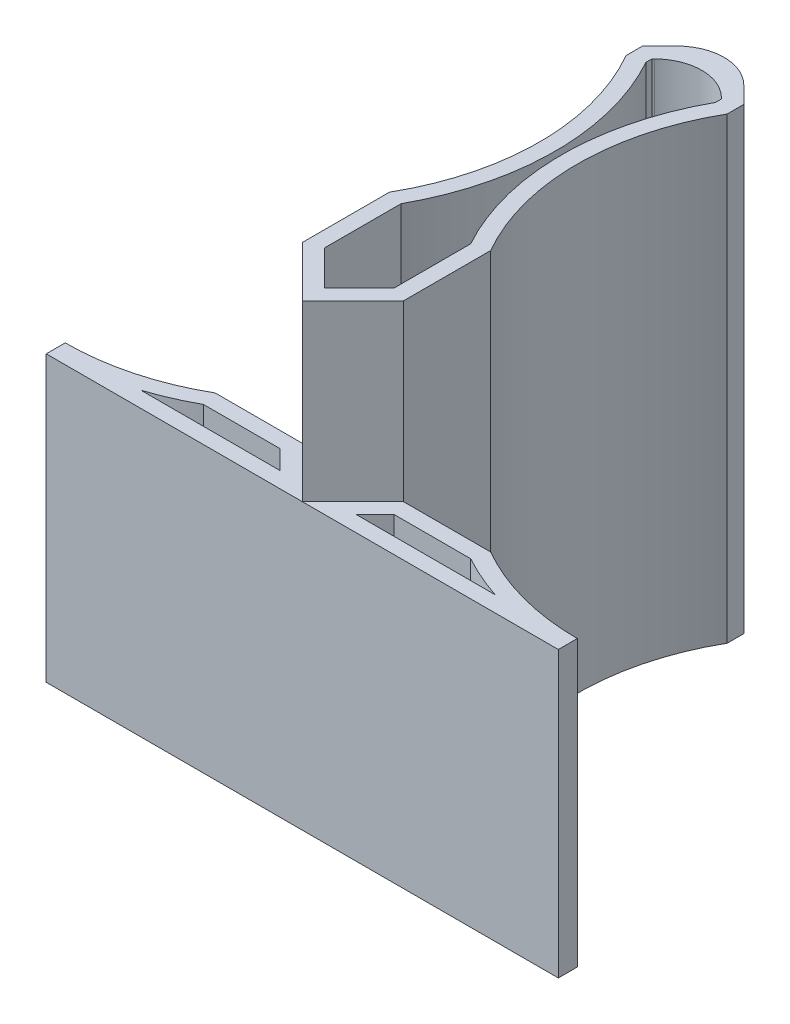
SolidWorks part; units mm, degrees
ref_plane "Front Plane" through (0, 0, 0) normal (0, 0, 1) x (1, 0, 0)
ref_plane "Top Plane" through (0, 0, 0) normal (0, 1, 0) x (1, 0, 0)
ref_plane "Right Plane" through (0, 0, 0) normal (1, 0, 0) x (0, 0, -1)
sketch "Sketch1" plane through (0, 0, 0) normal (0, 1, 0) x (1, 0, 0)
  line L0 (23.7595, 41.275) -> (41.275, 41.275) construction
  line L1 (-41.275, -41.275) -> (-23.7595, -41.275) construction
  line L2 (-41.275, -41.275) -> (-41.275, -23.7595) construction
  line L3 (-41.275, 41.275) -> (-23.7595, 41.275) construction
  line L4 (41.275, -41.275) -> (41.275, -23.7595) construction
  line L5 (-41.275, -41.275) -> (41.275, 41.275) construction
  line L6 (-41.275, 41.275) -> (41.275, -41.275) construction
  line L7 (41.275, 23.7595) -> (41.275, 41.275) construction
  line L8 (-41.275, 23.7595) -> (-41.275, 41.275) construction
  line L9 (23.7595, -41.275) -> (41.275, -41.275) construction
  line L10 (24.7569, 45.085) -> (45.085, 45.085) construction
  line L11 (45.085, 24.7569) -> (45.085, 45.085) construction
  line L12 (45.085, -45.085) -> (45.085, -24.7569) construction
  line L13 (24.7569, -45.085) -> (45.085, -45.085) construction
  line L14 (-45.085, -45.085) -> (-24.7569, -45.085) construction
  line L15 (-45.085, -45.085) -> (-45.085, -24.7569) construction
  line L16 (-45.085, 24.7569) -> (-45.085, 45.085) construction
  line L17 (-45.085, 45.085) -> (-24.7569, 45.085) construction
  line L19 (-51.435, -51.435) -> (51.435, -51.435) construction
  line L20 (-51.435, -51.435) -> (-51.435, 51.435) construction
  line L21 (-51.435, 51.435) -> (51.435, 51.435) construction
  line L22 (51.435, -51.435) -> (51.435, 51.435) construction
  line L23 (-51.435, -51.435) -> (51.435, 51.435) construction
  line L24 (-51.435, 51.435) -> (51.435, -51.435) construction
  arc A1 (-41.275, 23.7595) -> (-41.275, -23.7595) centre (0, 0) ccw construction
  arc A2 (23.7595, 41.275) -> (-23.7595, 41.275) centre (0, 0) ccw construction
  arc A3 (-23.7595, -41.275) -> (23.7595, -41.275) centre (0, 0) ccw construction
  arc A4 (41.275, -23.7595) -> (41.275, 23.7595) centre (0, 0) ccw construction
  arc A5 (45.085, -24.7569) -> (45.085, 24.7569) centre (0, 0) ccw construction
  arc A6 (-24.7569, -45.085) -> (24.7569, -45.085) centre (0, 0) ccw construction
  arc A7 (-45.085, 24.7569) -> (-45.085, -24.7569) centre (0, 0) ccw construction
  arc A8 (24.7569, 45.085) -> (-24.7569, 45.085) centre (0, 0) ccw construction
  point P0 (0, 0)
  dimension "D1" = 82.55
  dimension "D2" = 82.55
  dimension "D3" = 95.25
  dimension "D4" = 3.81
sketch "Sketch2" plane through (0, 0, 0) normal (0, 0, 1) x (1, 0, 0)
  line L0 (0, 48) -> (0, 0) construction
  line L1 (0, 0) -> (0, -9.15) construction
  line L2 (0, 48) -> (0, 82.925) construction
  dimension "Cage height" = 48
  dimension "Plate height" = 34.925
  dimension "D1" = 57.15
  dimension "D2" = 9.15
sketch "Sketch13" plane through (0, 0, 0) normal (0, 1, 0) x (1, 0, 0)
  line L0 (-51.435, -51.435) -> (51.435, -51.435) construction
  line L1 (-41.275, -41.275) -> (-23.7595, -41.275) construction
  line L2 (-41.275, -41.275) -> (-41.275, -23.7595) construction
  line L4 (-51.435, -51.435) -> (0, -51.435)
  line L5 (-41.275, -41.275) -> (-23.7595, -41.275)
  line L6 (-41.275, -41.275) -> (-41.275, -23.7595)
  line L9 (0, -47.625) -> (0, -51.435)
  line L10 (-51.435, 51.435) -> (51.435, -51.435) construction
  line L11 (-41.275, 23.7595) -> (-41.275, 41.275) construction
  line L12 (-51.435, -51.435) -> (-51.435, 51.435) construction
  line L13 (-51.435, 51.435) -> (-41.275, 41.275)
  line L14 (-41.275, 23.7595) -> (-41.275, 41.275)
  line L15 (-51.435, -51.435) -> (-51.435, 51.435)
  arc A0 (-23.7595, -41.275) -> (23.7595, -41.275) centre (0, 0) ccw construction
  arc A2 (-23.7595, -41.275) -> (0, -47.625) centre (0, 0) ccw
  arc A4 (-41.275, 23.7595) -> (-41.275, -23.7595) centre (0, 0) ccw construction
  arc A5 (-41.275, 23.7595) -> (-41.275, -23.7595) centre (0, 0) ccw
extrude "Boss-Extrude2" add sketch "Sketch13" along normal up to vertex (82.925 mm away) and the other way up to vertex (9.15 mm away) up to point (0, 82.925, 0) other way up to point (0, -9.15, 0)
sketch "Sketch15" plane through (0, 82.925, 0) normal (0, 1, 0) x (1, 0, 0)
  line L0 (0, 0) -> (-51.435, -51.435)
  line L1 (-51.435, -51.435) -> (0, -51.435)
  line L2 (0, -51.435) -> (0, 0)
  line L3 (-51.435, -51.435) -> (51.435, -51.435) construction
extrude "Cut-Extrude2" cut sketch "Sketch15" against normal up to vertex (34.925 mm away) up to point (0, 48, 0)
mirror "Mirror1" about plane through (-51.435, 82.925, 51.435) normal (1, 0, 0) of "Boss-Extrude2", "Cut-Extrude2"
sketch "Sketch16" plane through (0, -9.15, 0) normal (0, -1, 0) x (1, 0, 0)
  line L1 (-51.435, -51.435) -> (51.435, -51.435) construction
  circle A5 centre (-51.435, -13.335) radius 1.35
  dimension "D1" = 2.7
  dimension "D2" = 38.1
extrude "Cut-Extrude3" cut sketch "Sketch16" against normal blind 31.75
sketch "Sketch17" plane through (0, 82.925, 0) normal (0, 1, 0) x (1, 0, 0)
  line L0 (7.0944, 7.0944) -> (-7.0944, -7.0944)
  line L1 (7.0944, 7.0944) -> (-44.3406, 58.5294)
  line L2 (-7.0944, -7.0944) -> (-51.435, 37.2462)
  line L3 (-44.3406, 58.5294) -> (-51.435, 51.435)
  line L4 (-41.275, -41.275) -> (41.275, 41.275) construction
  line L5 (-61.595, 41.275) -> (-51.435, 51.435) construction
  line L6 (-51.435, -51.435) -> (-51.435, 51.435) construction
  line L7 (-51.435, 7.7321) -> (-51.435, 82.5591) construction
  line L8 (-95.7756, -7.0944) -> (-51.435, 37.2462)
  line L9 (-58.5294, 58.5294) -> (-51.435, 51.435)
  line L10 (-109.9644, 7.0944) -> (-58.5294, 58.5294)
  line L11 (-109.9644, 7.0944) -> (-95.7756, -7.0944)
  dimension "D1" = 20.066
extrude "Cut-Extrude4" cut sketch "Sketch17" against normal through all
sketch "Sketch18" plane through (0, 82.925, 0) normal (0, 1, 0) x (1, 0, 0)
  line L19 (-58.42, -24.5934) -> (-58.42, -39.9599)
  line L20 (-58.42, -39.9599) -> (-51.435, -46.9449)
  line L21 (-51.435, -46.9449) -> (-44.45, -39.9599)
  line L22 (-44.45, -39.9599) -> (-44.45, -24.5934)
  line L27 (-58.42, -24.5934) -> (-58.42, -39.9599)
  line L28 (-58.42, -39.9599) -> (-51.435, -46.9449)
  line L29 (-51.435, -46.9449) -> (-44.45, -39.9599)
  line L30 (-44.45, -39.9599) -> (-44.45, -24.5934)
  line L32 (-62.9101, -44.45) -> (-78.2766, -44.45)
  line L33 (-87.0077, -48.26) -> (-59.1001, -48.26)
  line L34 (-59.1001, -48.26) -> (-62.9101, -44.45)
  line L35 (-62.9101, -44.45) -> (-78.2766, -44.45)
  line L36 (-87.0077, -48.26) -> (-59.1001, -48.26)
  line L37 (-59.1001, -48.26) -> (-62.9101, -44.45)
  line L42 (-24.5934, -44.45) -> (-39.9599, -44.45)
  line L43 (-39.9599, -44.45) -> (-43.7699, -48.26)
  line L44 (-43.7699, -48.26) -> (-15.8623, -48.26)
  line L45 (-24.5934, -44.45) -> (-39.9599, -44.45)
  line L46 (-39.9599, -44.45) -> (-43.7699, -48.26)
  line L47 (-43.7699, -48.26) -> (-15.8623, -48.26)
  line L48 (-44.45, 25.7711) -> (-51.435, 32.7561)
  line L49 (-44.45, 25.7711) -> (-51.435, 32.7561)
  line L50 (-51.435, 32.7561) -> (-58.42, 25.7711)
  line L51 (-51.435, 32.7561) -> (-58.42, 25.7711)
  line L52 (-58.42, 25.7711) -> (-58.42, 24.5934)
  line L53 (-58.42, 25.7711) -> (-58.42, 24.5934)
  line L54 (-44.45, 24.5934) -> (-44.45, 25.7711)
  line L55 (-44.45, 24.5934) -> (-44.45, 25.7711)
  arc A5 (-87.0077, -48.26) -> (-78.2766, -44.45) centre (-102.87, 0) ccw
  arc A7 (-58.42, -24.5934) -> (-58.42, 24.5934) centre (-102.87, 0) ccw
  arc A8 (-44.45, 24.5934) -> (-44.45, -24.5934) centre (0, 0) ccw
  arc A10 (-58.42, -24.5934) -> (-58.42, 24.5934) centre (-102.87, 0) ccw
  arc A11 (-44.45, 24.5934) -> (-44.45, -24.5934) centre (0, 0) ccw
  arc A12 (-87.0077, -48.26) -> (-78.2766, -44.45) centre (-102.87, 0) ccw
  arc A14 (-24.5934, -44.45) -> (-15.8623, -48.26) centre (0, 0) ccw
  arc A15 (-24.5934, -44.45) -> (-15.8623, -48.26) centre (0, 0) ccw
  dimension "D1" = 3.175
  dimension "D2" = 3.175
  dimension "D3" = 3.175
extrude "Cut-Extrude5" cut sketch "Sketch18" against normal up to surface (60.325 mm away) contours A11 L55 L49 L51 L53 A10 L27 L28 L29 L30 region at (-51.435, 82.925, 12.1349) up to face at (-51.435, 22.6, -14.685)
sketch "Sketch22" plane through (0, 0, 0) normal (0, 1, 0) x (1, 0, 0)
  line L0 (-51.435, -51.435) -> (-51.435, 51.435) construction
  line L1 (-51.435, 51.435) -> (51.435, 51.435) construction
  circle A0 centre (-51.435, -12.065) radius 1.85
  dimension "D1" = 3.7
  dimension "D2" = 63.5
extrude "Cut-Extrude7" cut sketch "Sketch22" against normal through all both and the other way through all
sketch "Sketch20" plane through (0, 22.6, 0) normal (0, 1, 0) x (1, 0, 0)
  line L7 (-56.039, 19.685) -> (-46.831, 19.685)
  line L9 (-47.3448, -18.415) -> (-55.5252, -18.415)
  line L24 (-44.45, 24.5934) -> (-44.45, 25.7711)
  line L25 (-44.45, 25.7711) -> (-51.435, 32.7561)
  line L26 (-51.435, 32.7561) -> (-58.42, 25.7711)
  line L27 (-58.42, 25.7711) -> (-58.42, 24.5934)
  line L28 (-58.42, -24.5934) -> (-58.42, -39.9599)
  line L29 (-58.42, -39.9599) -> (-51.435, -46.9449)
  line L30 (-51.435, -46.9449) -> (-44.45, -39.9599)
  line L31 (-44.45, -39.9599) -> (-44.45, -24.5934)
  line L32 (-44.45, 24.5934) -> (-44.45, 25.7711)
  line L33 (-44.45, 25.7711) -> (-51.435, 32.7561)
  line L34 (-51.435, 32.7561) -> (-58.42, 25.7711)
  line L35 (-58.42, 25.7711) -> (-58.42, 24.5934)
  line L36 (-58.42, -24.5934) -> (-58.42, -39.9599)
  line L37 (-58.42, -39.9599) -> (-51.435, -46.9449)
  line L38 (-51.435, -46.9449) -> (-44.45, -39.9599)
  line L39 (-44.45, -39.9599) -> (-44.45, -24.5934)
  arc A0 (-58.42, -24.5934) -> (-58.42, 24.5934) centre (-102.87, 0) ccw construction
  arc A1 (-47.3448, -18.415) -> (-44.45, -24.5934) centre (0, 0) ccw
  arc A5 (-58.42, -24.5934) -> (-58.42, 24.5934) centre (-102.87, 0) ccw construction
  arc A9 (-44.45, 24.5934) -> (-44.45, -24.5934) centre (0, 0) ccw construction
  arc A11 (-44.45, 24.5934) -> (-44.45, -24.5934) centre (0, 0) ccw construction
  arc A13 (-58.42, -24.5934) -> (-58.42, 24.5934) centre (-102.87, 0) ccw
  arc A14 (-44.45, 24.5934) -> (-44.45, -24.5934) centre (0, 0) ccw
  arc A15 (-58.42, -24.5934) -> (-55.5252, -18.415) centre (-102.87, 0) ccw
  arc A16 (-44.45, 24.5934) -> (-46.831, 19.685) centre (0, 0) ccw
  arc A18 (-56.039, 19.685) -> (-58.42, 24.5934) centre (-102.87, 0) ccw
  circle A19 centre (-51.435, 13.335) radius 1.35 construction
  circle A20 centre (-51.435, -12.065) radius 1.85 construction
  dimension "D2" = 6.35
  dimension "D5" = 6.35
  dimension "D1" = 0
extrude "Cut-Extrude9" cut sketch "Sketch18<3>" against normal through all contours L36 L37 L35 A12 | L45 L46 L47 A15
sketch "Sketch18<3>" plane through (0, 82.925, 0) normal (0, 1, 0) x (1, 0, 0) same geometry as "Sketch18"
extrude "Cut-Extrude10" cut sketch "Sketch20" against normal through all
fillet "Fillet2" radius 9.525 2 edges at (-51.435, 36.8875, -37.2462) (-51.435, 36.8875, -32.7561)
equation "\"tightTol\" = 0.005in"
equation "\"normTol\" = 0.01in"
equation "\"looseTol\" = 0.02in"
equation "\"Cage height@Sketch2\"=48mm"
equation "\"Plate height@Sketch2\"=1.375"
equation "\"D1@Sketch17\"=0.75in+2*\"looseTol\""
equation "\"D1@Sketch22\"=3.7mm"
equation "\"D1@Sketch16\"=2.7mm"
